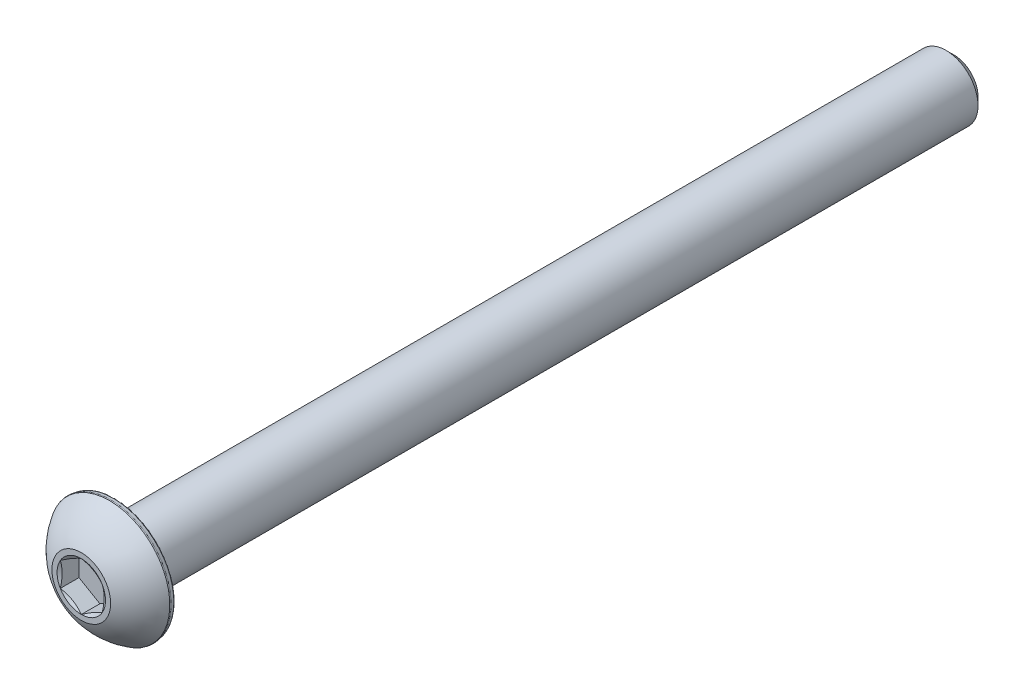
SolidWorks part; units mm, degrees
material "Alloy Steel"
ref_plane "Front Plane" through (0, 0, 0) normal (0, 0, 1) x (1, 0, 0)
ref_plane "Top Plane" through (0, 0, 0) normal (0, 1, 0) x (1, 0, 0)
ref_plane "Right Plane" through (0, 0, 0) normal (1, 0, 0) x (0, 0, -1)
sketch "Sketch1" plane through (0, 0, 0) normal (1, 0, 0) x (0, 0, -1)
  line L0 (-33.0327, 0) -> (33.0327, 0) construction
  line L1 (-33.0327, 0) -> (-33.0327, 4.5847)
  line L2 (-33.0327, 4.5847) -> (-30.4673, 4.5847)
  line L3 (-30.4673, 4.5847) -> (-30.4673, 2.413)
  line L4 (-30.4673, 2.413) -> (33.0327, 2.413)
  line L5 (33.0327, 2.413) -> (33.0327, 0)
  line L6 (33.0327, 0) -> (33.0327, -2.413) construction
  point P2 (0, 0)
  point P4 (32.239, 0)
  point P9 (31.8421, 2.413)
  point P10 (31.8421, -2.413)
  point P12 (-19.0055, 2.413)
  point P13 (23.8633, 2.413)
  point P14 (-21.2979, 2.413)
  point P15 (-31.6217, 0)
  dimension "Head Height" = 2.5654
  dimension "Head Diameter" = 9.1694
  dimension "Length" = 63.5
  dimension "Screw Size Decimal Equivalent" = 4.826
  dimension "Thread Pitch" = 0.7937
  dimension "D1" = 1.1906
  dimension "D2" = 1.411
  dimension "D3" = 9.1694
  dimension "D4" = 9.1694
  dimension "D5" = 11.4618
sketch "Sketch2" plane through (0, 0, 0) normal (0, 0, 1) x (1, 0, 0)
  line L0 (0, 2.413) -> (0, 0) construction
  line L1 (0, 1.8331) -> (-1.5875, 0.9165)
  line L2 (-1.5875, 0.9165) -> (-1.5875, -0.9165)
  line L3 (-1.5875, -0.9165) -> (0, -1.8331)
  line L4 (0, -1.8331) -> (1.5875, -0.9165)
  line L5 (1.5875, -0.9165) -> (1.5875, 0.9165)
  line L6 (1.5875, 0.9165) -> (0, 1.8331)
  circle A0 centre (0, 0) radius 1.5875 construction
  circle A1 centre (0, 0) radius 2.2225
  point P10 (0, 2.2225)
  dimension "D1" = 4.445
  dimension "Drive Size" = 3.175
sketch "Sketch3" plane through (0, 0, 0) normal (1, 0, 0) x (0, 0, -1)
  line L0 (-33.0327, 0) -> (-33.0327, 2.2225)
  line L1 (-33.0327, 0) -> (-33.0327, 4.5847) construction
  line L2 (-33.0327, 4.5847) -> (-30.4673, 4.5847) construction
  line L3 (-30.8521, 4.5847) -> (-30.4673, 4.5168)
  line L4 (-30.4673, 4.5847) -> (-30.4673, 2.413) construction
  line L5 (-30.4673, 4.5168) -> (-30.4673, 2.413)
  line L6 (-33.0327, 0) -> (33.0327, 0) construction
  line L7 (-33.0327, 0) -> (33.0327, 0)
  line L8 (33.0327, 0) -> (33.0327, 1.8177)
  line L9 (33.0327, 2.413) -> (33.0327, 0) construction
  line L10 (33.0327, 1.8177) -> (32.4374, 2.413)
  line L11 (-30.4673, 2.413) -> (33.0327, 2.413) construction
  line L12 (32.4374, 2.413) -> (-30.4673, 2.413)
  arc A0 (-33.0327, 2.2225) -> (-30.8521, 4.5847) centre (-28.2553, 0) cw
  dimension "D1" = 0.3848
  dimension "D2" = 10
  dimension "D3" = 45
  dimension "D4" = 0.5953
revolve "Revolve1" add sketch "Sketch3" angle 360 about L7
sketch "Sketch4" plane through (0, 0, 33.0327) normal (0, 0, 1) x (1, 0, 0)
  line L0 (-1.5875, -0.9165) -> (0, -1.8331) construction
  line L1 (-1.5875, 0.9165) -> (-1.5875, -0.9165) construction
  line L2 (0, 1.8331) -> (-1.5875, 0.9165) construction
  line L3 (1.5875, 0.9165) -> (0, 1.8331) construction
  line L4 (1.5875, -0.9165) -> (1.5875, 0.9165) construction
  line L5 (0, -1.8331) -> (1.5875, -0.9165) construction
  line L6 (-1.5875, -0.9165) -> (0, -1.8331)
  line L7 (-1.5875, 0.9165) -> (-1.5875, -0.9165)
  line L8 (0, 1.8331) -> (-1.5875, 0.9165)
  line L9 (1.5875, 0.9165) -> (0, 1.8331)
  line L10 (1.5875, -0.9165) -> (1.5875, 0.9165)
  line L11 (0, -1.8331) -> (1.5875, -0.9165)
extrude "Cut-Extrude1" cut sketch "Sketch4" against normal up to vertex (1.411 mm away) up to point (0, 0, 31.6217)
sketch "Sketch5" plane through (0, 0, 33.0327) normal (0, 0, 1) x (1, 0, 0)
  circle A0 centre (0, 0) radius 1.8331
extrude "Cut-Extrude2" cut sketch "Sketch5" against normal up to vertex (1.411 mm away) draft 60 up to point (0, 0, 31.6217)
fillet "Fillet1" radius 0.1283 2 edges at (4.5847, 0, 30.8521) (4.5168, 0, 30.4673)
split "Split1" [suppressed] bodies to split 106
sketch "Sketch6" [suppressed] plane through (0, 0, -33.0327) normal (0, 0, -1) x (-1, 0, 0)
  circle A0 centre (0, 0) radius 2.413 construction
  circle A1 centre (0, 0) radius 2.413
curve "Helix/Spiral1" [suppressed] pitch 0.7937 height 64.2938 turns 81
sketch "Sketch7" [suppressed] plane through (0, 0, 0) normal (1, 0, 0) x (0, 0, -1)
  line L0 (32.9831, 2.4989) -> (33.38, 1.8115) construction
  line L1 (33.38, 1.8115) -> (33.7768, 2.4989) construction
  line L2 (33.7768, 2.4989) -> (32.9831, 2.4989) construction
  line L3 (33.0079, 2.456) -> (33.752, 2.456)
  line L4 (33.752, 2.456) -> (33.4296, 1.8974)
  line L5 (33.4296, 1.8974) -> (33.3304, 1.8974)
  line L6 (33.3304, 1.8974) -> (33.0079, 2.456)
  line L7 (33.38, 1.8974) -> (33.38, 1.8115) construction
  line L8 (33.0327, 2.413) -> (33.7272, 2.413) construction
  line L9 (33.38, 2.4989) -> (33.38, 2.413) construction
  point P12 (33.38, 2.456)
  dimension "D1" = 0.7937
  dimension "D2" = 0.0992
sweep "Cut-Sweep1" [suppressed] cut profiles "Sketch7" path "Helix/Spiral1"
sketch "Sketch8" [suppressed] plane through (0, 0, 30.4673) normal (0, 0, -1) x (-1, 0, 0)
  circle A0 centre (0, 0) radius 2.4989
extrude "Boss-Extrude1" [suppressed] add sketch "Sketch8" along normal up to vertex draft 45 up to point (0, 2.413, -31.8421)
equation "\"D1@Sketch1\"=\"Thread Pitch@Sketch1\"*1.5"
equation "\"D2@Sketch1\"=0.55*\"Head Height@Sketch1\""
equation "\"D1@Sketch2\"=\"Drive Size@Sketch2\"*1.4"
equation "\"D1@Sketch3\"=0.15*\"Head Height@Sketch1\""
equation "\"D4@Sketch3\"=0.75*\"Thread Pitch@Sketch1\""
equation "\"D1@Fillet1\"=.05*\"Head Height@Sketch1\""
equation "\"D4@Helix/Spiral1\"=\"Thread Pitch@Sketch1\""
equation "\"D2@Sketch7\"=\"D1@Sketch7\"/8"
equation "\"D1@Sketch7\"=\"Thread Pitch@Sketch1\""
equation "\"D3@Sketch1\"=\"Head Diameter@Sketch1\""
equation "\"D4@Sketch1\"=\"Head Diameter@Sketch1\""
equation "\"D5@Sketch1\"=\"D3@Sketch1\"*1.25"
